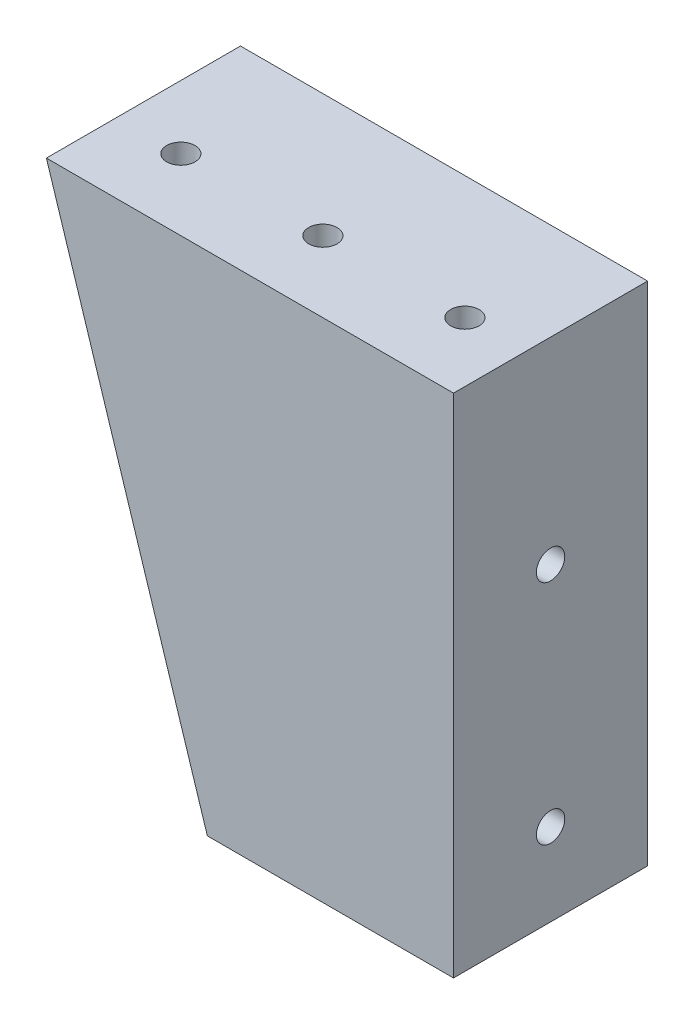
SolidWorks part; units mm, degrees
ref_plane "Front Plane" through (0, 0, 0) normal (0, 0, 1) x (1, 0, 0)
ref_plane "Top Plane" through (0, 0, 0) normal (0, 1, 0) x (1, 0, 0)
ref_plane "Right Plane" through (0, 0, 0) normal (1, 0, 0) x (0, 0, -1)
sketch "Sketch3" plane through (0, 0, 0) normal (0, 0, 1) x (1, 0, 0)
  line L0 (380.7064, -77.5128) -> (380.7064, -131.0128)
  line L1 (380.7064, -77.5128) -> (337.7064, -77.5128)
  line L2 (380.7064, -131.0128) -> (354.7064, -131.0128)
  line L3 (337.7064, -77.5128) -> (354.7064, -131.0128)
  dimension "D1" = 53.5
  dimension "D2" = 43
  dimension "D3" = 26
extrude "Boss-Extrude2" add sketch "Sketch3" along normal blind 15
ref_plane "Plane7" through (380.7064, 0, 0) normal (1, 0, 0) x (0, 0, -1)
ref_plane "Plane8" through (0, -77.5128, 0) normal (0, 1, 0) x (1, 0, 0)
sketch "Sketch5" plane through (0, -77.5128, 0) normal (0, 1, 0) x (1, 0, 0)
  line L1 (337.7064, -15) -> (337.7064, 0) construction
  line L4 (380.7064, -15) -> (380.7064, 0) construction
  circle A0 centre (344.4064, -7.5) radius 1.5
  circle A1 centre (344.4064, -7.5) radius 1.5
  circle A2 centre (359.4064, -7.5) radius 1.5
  circle A3 centre (374.4064, -7.5) radius 1.5
  dimension "D1" = 6.7
  dimension "D2" = 15
  dimension "D3" = 15
  dimension "D4" = 6.3
extrude "Cut-Extrude3" cut sketch "Sketch5" against normal blind 8 contours A0 | A2 | A3 region at (344.4064, -77.5128, 7.5) region at (359.4064, -77.5128, 7.5) region at (374.4064, -77.5128, 7.5)
ref_plane "Plane10" through (0, 0, 0) normal (0, 0, -1) x (-1, 0, 0)
sketch "Sketch7" plane through (0, 0, 0) normal (0, 0, -1) x (-1, 0, 0)
  line L0 (-380.7064, -77.5128) -> (-337.7064, -77.5128)
  line L1 (-337.7064, -77.5128) -> (-354.7064, -131.0128)
  line L2 (-354.7064, -131.0128) -> (-380.7064, -131.0128)
  line L3 (-380.7064, -131.0128) -> (-380.7064, -77.5128)
extrude "Boss-Extrude4" add sketch "Sketch7" along normal blind 5.5
ref_plane "Plane11" through (380.7064, 0, 0) normal (1, 0, 0) x (0, 0, -1)
sketch "Sketch8" plane through (380.7064, 0, 0) normal (1, 0, 0) x (0, 0, -1)
  line L0 (-4.75, -77.5128) -> (-4.75, -131.0128)
  line L1 (-15, -77.5128) -> (5.5, -77.5128) construction
  line L2 (-15, -131.0128) -> (5.5, -131.0128) construction
  circle A0 centre (-4.75, -98.3128) radius 1.5
  circle A1 centre (-4.75, -122.3128) radius 1.5
extrude "Cut-Extrude4" cut sketch "Sketch8" against normal blind 10 contours L0 A0 | L0 A0 | L0 A1 | A1 region at (380.7064, -98.3128, 4.1134) region at (380.7064, -122.3128, 4.1134) region at (380.7064, -98.3128, 5.3866)
ref_plane "Plane12" through (0, -131.0128, 0) normal (0, -1, 0) x (-1, 0, 0)
sketch "Sketch9" plane through (0, -131.0128, 0) normal (0, -1, 0) x (-1, 0, 0)
  line L0 (-354.7064, -4.75) -> (-380.5043, -4.75)
  line L1 (-354.7064, -15) -> (-354.7064, 5.5) construction
  circle A0 centre (-361.7064, -4.75) radius 1.5
  circle A1 centre (-373.7064, -4.75) radius 1.5
extrude "Cut-Extrude5" cut sketch "Sketch9" against normal blind 7 contours L0 A1 | L0 A1 | L0 A0 | L0 A0 region at (361.7064, -131.0128, 5.3866) region at (361.7064, -131.0128, 4.1134) region at (373.7064, -131.0128, 5.3866) region at (373.7064, -131.0128, 4.1134)
extrude "Cut-Extrude6" cut sketch "Sketch5<4>" against normal blind 10 contours A2 | A3 region at (359.4064, -77.5128, 7.5) region at (374.4064, -77.5128, 7.5)
sketch "Sketch5<4>" plane through (0, -77.5128, 0) normal (0, 1, 0) x (1, 0, 0) same geometry as "Sketch5"
ref_plane "Plane13" through (0, 0, 15) normal (0, 0, 1) x (1, 0, 0)
sketch "Sketch10" plane through (0, 0, 15) normal (0, 0, 1) x (1, 0, 0)
  line L1 (356.5124, -84.0481) -> (362.1124, -84.0481)
  line L2 (356.5124, -84.0481) -> (356.5124, -86.4481)
  line L3 (356.5124, -86.4481) -> (362.1124, -86.4481)
  line L4 (362.1124, -84.0481) -> (362.1124, -86.4481)
  line L5 (371.5837, -84.0481) -> (377.0837, -84.0481)
  line L6 (371.5837, -84.0481) -> (371.5837, -86.4481)
  line L7 (371.5837, -86.4481) -> (377.0837, -86.4481)
  line L8 (377.0837, -84.0481) -> (377.0837, -86.4481)
  dimension "D1" = 2.4
  dimension "D2" = 5.6
  dimension "D3" = 5.5
  dimension "D4" = 2.4
extrude "Cut-Extrude7" cut sketch "Sketch10" against normal blind 24
extrude "Boss-Extrude5" add sketch "Sketch10<3>" against normal blind 4.2
sketch "Sketch10<3>" plane through (0, 0, 15) normal (0, 0, 1) x (1, 0, 0) same geometry as "Sketch10"
